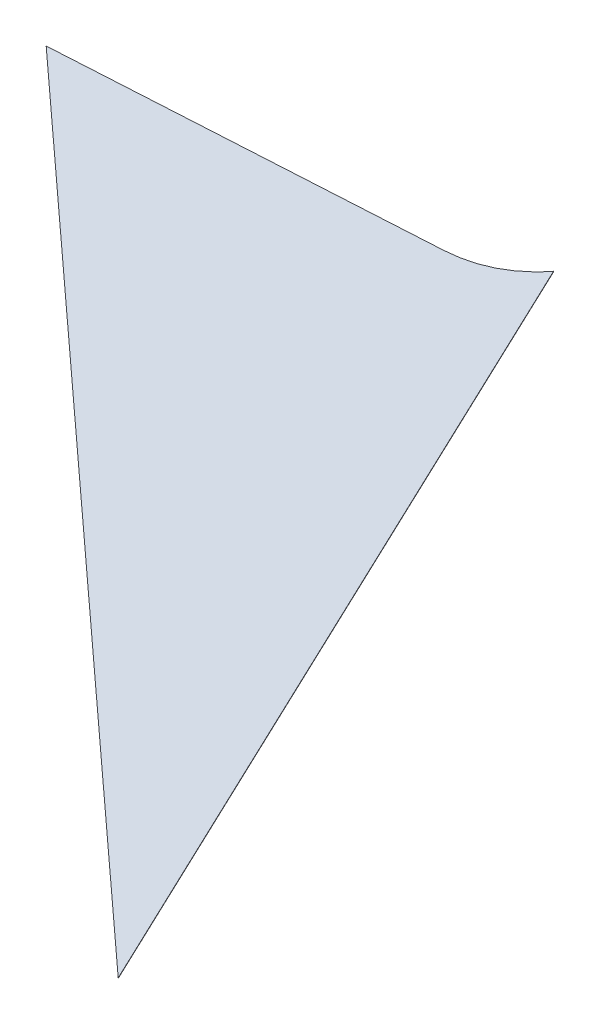
SolidWorks part; units mm, degrees
ref_plane "Front Plane" through (0, 0, 0) normal (0, 0, 1) x (1, 0, 0)
ref_plane "Top Plane" through (0, 0, 0) normal (0, 1, 0) x (1, 0, 0)
ref_plane "Right Plane" through (0, 0, 0) normal (1, 0, 0) x (0, 0, -1)
sketch "Tube Reference" plane through (-88.274, -606.3364, -992.3811) normal (0.0661, -0.7678, -0.6373) x (0.9973, 0.0713, 0.0175)
  line L0 (-198.1326, 66.9643) -> (198.1326, 66.9643) construction
  line L1 (235, 58.2094) -> (235, 577.288) construction
  line L2 (-198.1326, 66.9643) -> (198.1326, 66.9643)
  line L3 (235, 58.2094) -> (235, 577.288)
  ellipse E0 centre (198.1326, -15.0318) end of major axis (280.1326, -15.0318) minor radius 81.9961 (263.9946, 33.8145) -> (198.1326, 66.9643) ccw construction
  ellipse E1 centre (198.1326, -15.0318) end of major axis (280.1326, -15.0318) minor radius 81.9961 (263.9946, 33.8145) -> (198.1326, 66.9643) ccw
sketch "Sketch2" plane through (-88.274, -606.3364, -992.3811) normal (0.0661, -0.7678, -0.6373) x (0.9973, 0.0713, 0.0175)
  line L0 (-198.1326, 66.9643) -> (198.1326, 66.9643) construction
  line L1 (235, 58.2094) -> (235, 577.288) construction
  line L2 (40.5227, 66.9643) -> (198.1326, 66.9643)
  line L3 (235, 58.2094) -> (235, 287.1081)
  line L4 (235, 58.2094) -> (235, 577.288) construction
  line L5 (235, 287.1081) -> (40.5227, 66.9643)
  ellipse E0 centre (198.1326, -15.0318) end of major axis (280.1326, -15.0318) minor radius 81.9961 (263.9946, 33.8145) -> (198.1326, 66.9643) ccw construction
  ellipse E1 centre (198.1326, -15.0318) end of major axis (280.1326, -15.0318) minor radius 81.9961 (235, 58.2094) -> (198.1326, 66.9643) ccw
extrude "Boss-Extrude1" add sketch "Sketch2" along normal mid plane 0.1524
sketch "Sketch3" plane through (-88.274, -606.3364, -992.3811) normal (0.0661, -0.7678, -0.6373) x (0.9973, 0.0713, 0.0175)
  point P0 (206.4576, 154.3059)
